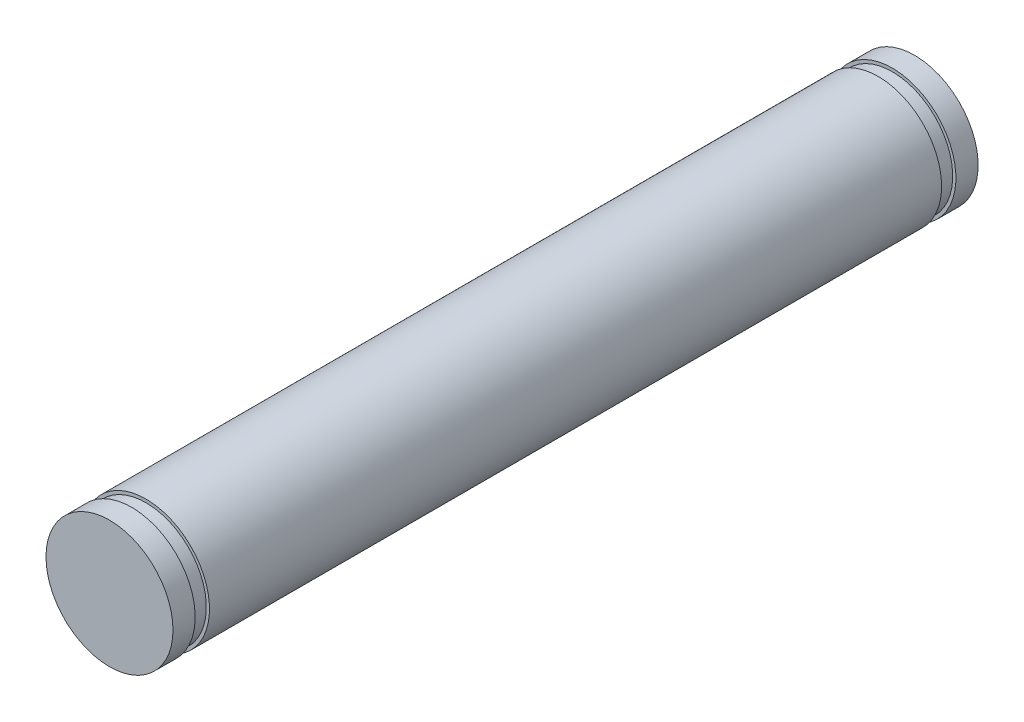
SolidWorks part; units mm, degrees
ref_plane "Front Plane" through (0, 0, 0) normal (0, 0, 1) x (1, 0, 0)
ref_plane "Top Plane" through (0, 0, 0) normal (0, 1, 0) x (1, 0, 0)
ref_plane "Right Plane" through (0, 0, 0) normal (1, 0, 0) x (0, 0, -1)
sketch "Sketch1" plane through (0, 0, 0) normal (0, 0, 1) x (1, 0, 0)
  line L0 (-4, 0) -> (4, 0) construction
  line L5 (0, 4) -> (0, -4) construction
  circle A1 centre (0, 0) radius 4
  point P7 (-4, 0)
  point P8 (4, 0)
  point P12 (0, -4)
  point P13 (0, 4)
  dimension "Diameter" = 8
sketch "Sketch2" plane through (0, 0, 0) normal (1, 0, 0) x (0, 0, -1)
  line L0 (-42, -4) -> (-42, 4) construction
  line L1 (50, -4) -> (-50, -4)
  line L2 (50, -4) -> (50, 4)
  line L3 (50, 4) -> (-50, 4)
  line L4 (-50, -4) -> (-50, 4)
  line L5 (50, -4) -> (-50, 4) construction
  line L6 (50, 4) -> (-50, -4) construction
  line L7 (42, -4) -> (42, 4) construction
  line L8 (-50, 3.44) -> (-49.44, 4) construction
  point P0 (0, 0)
  point P8 (-50, 4)
  point P9 (50, 4)
  point P14 (-42, 4)
  point P15 (-42, -4)
  point P16 (42, 4)
  point P17 (42, -4)
  point P25 (0, -4)
  dimension "Length" = 100
  dimension "D1" = 8
  dimension "D2" = 8
  dimension "Chamfer Typ," = 45
  dimension "D4" = 0.56
sketch "Sketch3" plane through (0, 0, 0) normal (0, 0, 1) x (1, 0, 0)
  circle A0 centre (0, 0) radius 4 construction
  circle A1 centre (0, 0) radius 4
extrude "Boss-Extrude1" add sketch "Sketch3" along normal up to vertex (50 mm away) and the other way up to vertex (50 mm away) up to point (0, 4, 50) other way up to point (0, 4, -50)
chamfer "Chamfer1" distance 0.56 angle 45 2 edges at (4, 0, -50) (4, 0, 50)
sketch "Sketch4" plane through (0, 0, 50) normal (0, 0, 1) x (1, 0, 0)
  circle A0 centre (0, 0) radius 14.5
  dimension "D1" = 29
extrude "Cut-Extrude1" cut sketch "Sketch4" against normal blind 24.638
sketch "Sketch5" plane through (0, 0, -50) normal (0, 0, -1) x (-1, 0, 0)
  circle A0 centre (0, 0) radius 6.5
  dimension "D1" = 13
extrude "Cut-Extrude2" cut sketch "Sketch5" against normal blind 24.638
sketch "Sketch6" plane through (0, 0, -25.362) normal (0, 0, -1) x (-1, 0, 0)
  circle A0 centre (0, 0) radius 4
  circle A1 centre (0, 0) radius 3.8
  circle A2 centre (0, 0) radius 4 construction
  dimension "D1" = 7.6
extrude "Cut-Extrude3" cut sketch "Sketch6" along normal blind 0.9 from offset 2.3 offset against normal yes
ref_plane "Plane1" through (0, 0, 0) normal (0, 0, -1) x (-1, 0, 0)
mirror "Mirror1" about plane through (0, 0, 0) normal (0, 0, -1) of "Cut-Extrude3"
equation "\"D1@Sketch2\"=\"Diameter@Sketch1\""
equation "\"D2@Sketch2\"=\"Diameter@Sketch1\""
equation "\"D1@Chamfer1\"=\"Diameter@Sketch1\"*.07"
equation "\"D4@Sketch2\"=\"Diameter@Sketch1\"*.07"
equation "\"D2@Chamfer1\"=\"Chamfer Typ,@Sketch2\""
